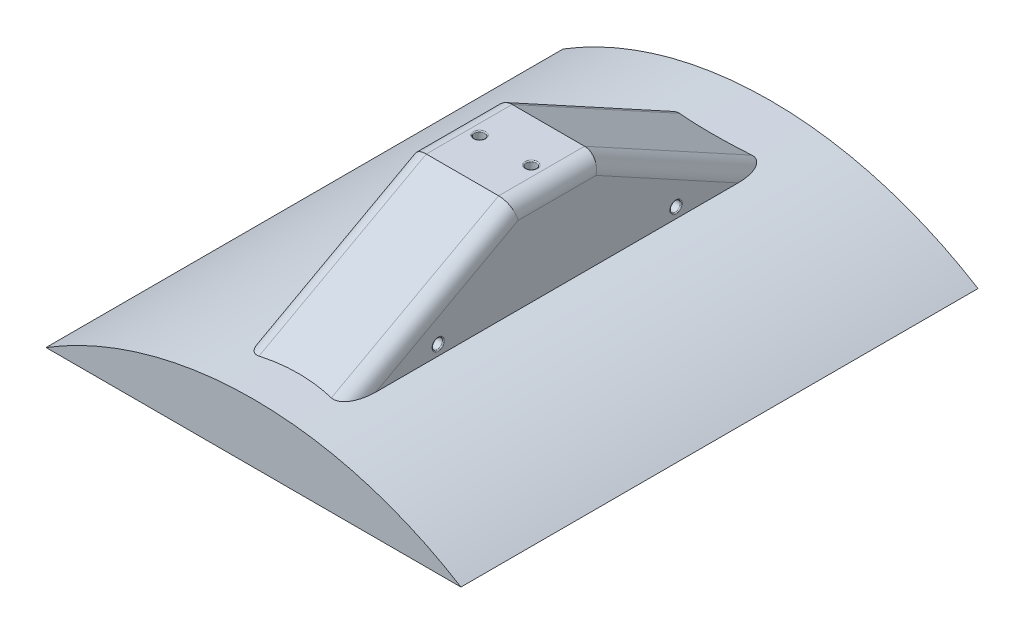
SolidWorks part; units mm, degrees
ref_plane "Front Plane" through (0, 0, 0) normal (0, 0, 1) x (1, 0, 0)
ref_plane "Top Plane" through (0, 0, 0) normal (0, 1, 0) x (1, 0, 0)
ref_plane "Right Plane" through (0, 0, 0) normal (1, 0, 0) x (0, 0, -1)
sketch "Sketch3" plane through (0, 0, 0) normal (0, 0, 1) x (1, 0, 0)
  line L0 (0, 0) -> (0, 8) construction
  line L1 (-10, 8) -> (10, 8)
  line L2 (-10, 8) -> (-10, -10)
  line L4 (10, 8) -> (10, -10)
  arc A0 (-10, -10) -> (10, -10) centre (0, -85.541) cw
  point P0 (0, 0)
  dimension "D3" = 76.2
  dimension "D1" = 20
  dimension "D2" = 18
  dimension "D4" = 8
  dimension "D5" = 18
extrude "Boss-Extrude1" add sketch "Sketch3" along normal blind 82.55
sketch "Sketch4" plane through (-10, 0, 0) normal (-1, 0, 0) x (0, 0, 1)
  line L0 (0, 0) -> (0, -10) construction
  line L1 (0, -10) -> (32.9728, 8)
  line L2 (82.55, 8) -> (0, 8) construction
  line L3 (82.55, -10) -> (0, -10) construction
  line L4 (6.6262, -10) -> (5.1049, -7.2132) construction
  line L5 (6.6262, -10) -> (34.4941, 5.2132) construction
  line L6 (5.1049, -7.2132) -> (32.9728, 8) construction
  line L7 (34.4941, 5.2132) -> (32.9728, 8) construction
  line L8 (0, -10) -> (0, 8)
  line L9 (0, 8) -> (32.9728, 8)
  line L10 (41.275, 8) -> (41.275, -10) construction
  line L11 (82.55, 8) -> (49.5772, 8)
  line L12 (82.55, -10) -> (82.55, 8)
  line L13 (82.55, -10) -> (49.5772, 8)
  dimension "D1" = 3.175
  dimension "D2" = 31.75
extrude "Cut-Extrude1" cut sketch "Sketch4" against normal through all
sketch "Sketch6" plane through (0, -7.7041, 4.2057) normal (0, 0.8777, -0.4792) x (1, 0, 0)
  line L0 (0, 3.4162) -> (0, -32.7745) construction
  line L1 (10, -32.7745) -> (-10, -32.7745) construction
  line L2 (0, -32.7745) -> (6.35, -32.7745) construction
  line L4 (6.35, -32.7745) -> (-6.4117, -32.7745)
  line L5 (6.35, -32.7745) -> (6.35, -1.0245)
  line L6 (6.35, -1.0245) -> (-6.4117, -1.0245)
  line L7 (-6.4117, -32.7745) -> (-6.4117, -1.0245)
  ellipse E0 centre (0, 162.4458) end of major axis (0, 321.4753) minor radius 76.2 (-10, 4.7916) -> (10, 4.7916) ccw construction
  dimension "D1" = 6.35
  dimension "D2" = 31.75
  dimension "D3" = 12.7617
fillet "Fillet3" radius 3 3 edges at (10, -1, 16.4864) (10, 8, 41.275) (10, -1, 66.0636) type face fillet first side face at (10, -1, 41.275) second side face at (0, -0.8352, 16.7882) second side face at (0, 8, 41.275) second side face at (0, -0.8352, 65.7618)
fillet "Fillet4" radius 3 3 edges at (-10, 8, 41.275) (-10, -1, 16.4864) (-10, -1, 66.0636) type face fillet first side face at (-10, -1, 41.275) second side face at (-1.5024, -0.7969, 65.6915) second side face at (-1.5, 8, 41.275) second side face at (-1.5024, -0.7969, 16.8585)
sketch "Sketch7" plane through (0, 8, 0) normal (0, 1, 0) x (1, 0, 0)
  line L0 (-7, -41.275) -> (-5, -41.275) construction
  line L1 (-7, -32.9728) -> (-7, -49.5772) construction
  line L2 (0, -32.9728) -> (0, -49.5772) construction
  line L3 (7, -49.5772) -> (-7, -49.5772) construction
  line L4 (7, -41.275) -> (5, -41.275) construction
  circle A0 centre (-5, -41.275) radius 1
  circle A1 centre (5, -41.275) radius 1
  dimension "D2" = 2
  dimension "D1" = 2
extrude "Cut-Extrude3" cut sketch "Sketch7" against normal blind 2
fillet "Fillet5" radius 0.2 2 edges at (-5, 8, 42.275) (5, 8, 40.275)
extrude "Cut-Extrude4" cut sketch "Sketch6" against normal blind 1.7
sketch "Sketch8" plane through (-10, 0, 0) normal (-1, 0, 0) x (0, 0, 1)
  line L0 (76.289, -10) -> (6.261, -10) construction
  line L1 (41.275, -10) -> (41.275, -8) construction
  line L2 (64.275, -8) -> (18.275, -8) construction
  circle A0 centre (18.275, -8) radius 1
  circle A1 centre (64.275, -8) radius 1
  dimension "D3" = 2
  dimension "D1" = 2
  dimension "D2" = 23
extrude "Cut-Extrude5" cut sketch "Sketch8" against normal blind 2
fillet "Fillet10" radius 0.2 2 edges at (-10, -7, 64.275) (-10, -9, 18.275)
mirror "Mirror3" about plane through (0, 0, 0) normal (1, 0, 0) of "Cut-Extrude5"
fillet "Fillet11" radius 0.2 2 edges at (10, -9, 18.275) (10, -7, 64.275)
shell "Shell10" thickness 1.5 removed face at (9.8, -8, 19.275) removed face at (9.8, -8, 65.275) removed face at (-9.8, -7, 18.275) removed face at (-9.8, -7, 64.275) removed face at (-0.0308, -7.9593, 5.5122) removed face at (6.35, -0.3527, 19.4462) removed face at (-6.4117, -0.3527, 19.4462) removed face at (-5, 7.8, 40.275) removed face at (5, 7.8, 40.275) removed face at (-0.0308, -1.0987, 19.8534) removed face at (0, -9.7482, 41.275) removed face at (-0.0308, 7.2539, 33.3801) removed face at (-8, -7, 64.275) removed face at (-8, -9, 18.275) removed face at (8, -9, 18.275) removed face at (8, -7, 64.275) removed face at (5, 6, 40.275) removed face at (-5, 6, 42.275)
sketch "Sketch9" plane through (0, 0, 0) normal (0, 0, 1) x (1, 0, 0)
  line L0 (-10, -10) -> (10, -10)
  arc A0 (-7, -9.6632) -> (-10, -10) centre (0, -85.541) ccw construction
  arc A1 (10, -10) -> (7, -9.6632) centre (0, -85.541) ccw construction
  arc A2 (7, -9.6632) -> (-7, -9.6632) centre (0, -85.541) ccw construction
  arc A3 (-7, -9.6632) -> (-10, -10) centre (0, -85.541) ccw
  arc A4 (10, -10) -> (7, -9.6632) centre (0, -85.541) ccw
  arc A5 (7, -9.6632) -> (-7, -9.6632) centre (0, -85.541) ccw
  circle A6 centre (0, -85.541) radius 76.2
extrude "Boss-Extrude4" add sketch "Sketch9" along normal blind 90 and the other way blind 10 contours A6
sketch "Sketch10" plane through (6.35, 0, 0) normal (-1, 0, 0) x (0, 0, 1)
  line L6 (5.8236, -8.5298) -> (33.3556, 6.5)
  line L7 (33.3556, 6.5) -> (33.773, 6.5)
  line L8 (33.773, 6.5) -> (33.7874, 6.5079)
  line L9 (33.7874, 6.5079) -> (32.9728, 8)
  line L10 (32.9728, 8) -> (5.1049, -7.2132)
  line L11 (5.1049, -7.2132) -> (5.8236, -8.5298)
  line L12 (5.8236, -8.5298) -> (33.3556, 6.5)
  line L13 (33.3556, 6.5) -> (33.773, 6.5)
  line L14 (33.773, 6.5) -> (33.7874, 6.5079)
  line L15 (33.7874, 6.5079) -> (32.9728, 8)
  line L16 (32.9728, 8) -> (5.1049, -7.2132)
  line L17 (5.1049, -7.2132) -> (5.8236, -8.5298)
  dimension "D1" = 0
extrude "Boss-Extrude5" add sketch "Sketch10" along normal up to vertex (12.7617 mm away) up to point (-6.4117, 8, 32.9728)
sketch "Sketch11" plane through (0, 0, 90) normal (0, 0, 1) x (1, 0, 0)
  line L0 (0, -9.341) -> (0, -85.541) construction
  line L1 (-98.8738, -20.7602) -> (98.8738, -20.7602)
  line L2 (-98.8738, -20.7602) -> (-98.8738, -168.8024)
  line L3 (-98.8738, -168.8024) -> (98.8738, -168.8024)
  line L4 (98.8738, -20.7602) -> (98.8738, -168.8024)
  circle A1 centre (0, -85.541) radius 76.2
  circle A2 centre (0, -85.541) radius 76.2
  point P8 (0, -20.7602)
  circle M7 centre (0, -85.541) radius 76.2
  dimension "D1" = 0
extrude "Cut-Extrude6" cut sketch "Sketch11" against normal through all both and the other way through all contours L1 M7 region at (0, -87.9848, 90)
